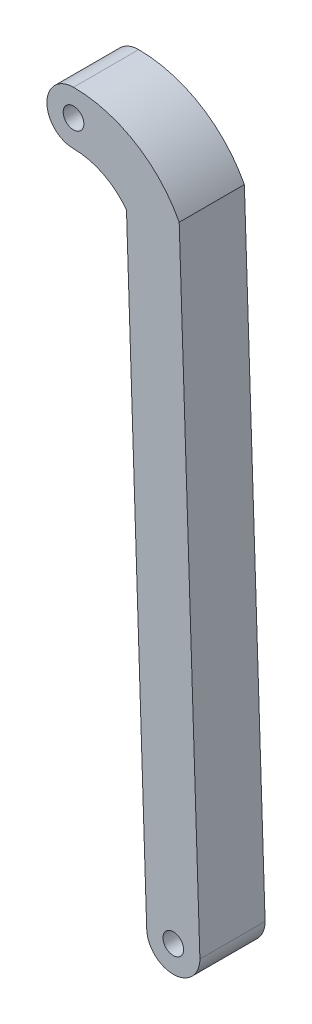
SolidWorks part; units mm, degrees
ref_plane "Plan de face" through (0, 0, 0) normal (0, 0, 1) x (1, 0, 0)
ref_plane "Plan de dessus" through (0, 0, 0) normal (0, 1, 0) x (1, 0, 0)
ref_plane "Plan de droite" through (0, 0, 0) normal (1, 0, 0) x (0, 0, -1)
sketch "Esquisse1" plane through (0, 0, 0) normal (0, 0, 1) x (1, 0, 0)
  line L2 (0, 0) -> (0, 100) construction
  line L3 (-15, 100) -> (0, 100) construction
  line L7 (-4, 0) -> (-7.0351, 91.9932)
  line L8 (4, 0) -> (0.8864, 94.3712)
  circle A14 centre (0, 0) radius 1.55
  circle A15 centre (-15, 100) radius 1.55
  arc A16 (-4, 0) -> (4, 0) centre (0, 0) ccw
  arc A17 (-15, 104) -> (-15, 96) centre (-15, 100) ccw
  arc A18 (-15, 104) -> (0.8864, 94.3712) centre (-15, 86.0802) cw
  arc A19 (-7.0351, 91.9932) -> (-15, 96) centre (-15, 86.0802) ccw
  point P4 (-5.5911, 89.2225)
  point P11 (0.9201, 92.0539)
  dimension "D1" = 3.1
  dimension "D2" = 3.1
  dimension "D3" = 100
  dimension "D5" = 8
  dimension "D6" = 8
  dimension "D4" = 15
extrude "Boss.-Extru.1" add sketch "Esquisse1" along normal blind 4.9 and the other way blind 4.9 contours A19 L7 A16 L8 A18 A17 A15 A14 region at (-2.6556, 53.289, 0)
sketch "Esquisse3" plane through (0, 0, 4.9) normal (0, 0, 1) x (1, 0, 0)
  line L0 (-7.0351, 91.9932) -> (-6.2728, 68.8885)
  line L1 (-4, 0) -> (-7.0351, 91.9932) construction
  line L2 (-6.2728, 68.8885) -> (1.7272, 68.8885)
  line L3 (4, 0) -> (0.8864, 94.3712) construction
  line L4 (1.7272, 68.8885) -> (0.8864, 94.3712)
  arc A0 (-15, 96) -> (-15, 104) centre (-15, 100) cw
  arc A1 (-15, 104) -> (0.8864, 94.3712) centre (-15, 86.0802) cw
  arc A2 (-15, 96) -> (-7.0351, 91.9932) centre (-15, 86.0802) cw
extrude "Enlèv. mat.-Extru.2" [suppressed] cut sketch "Esquisse3" against normal blind 3
